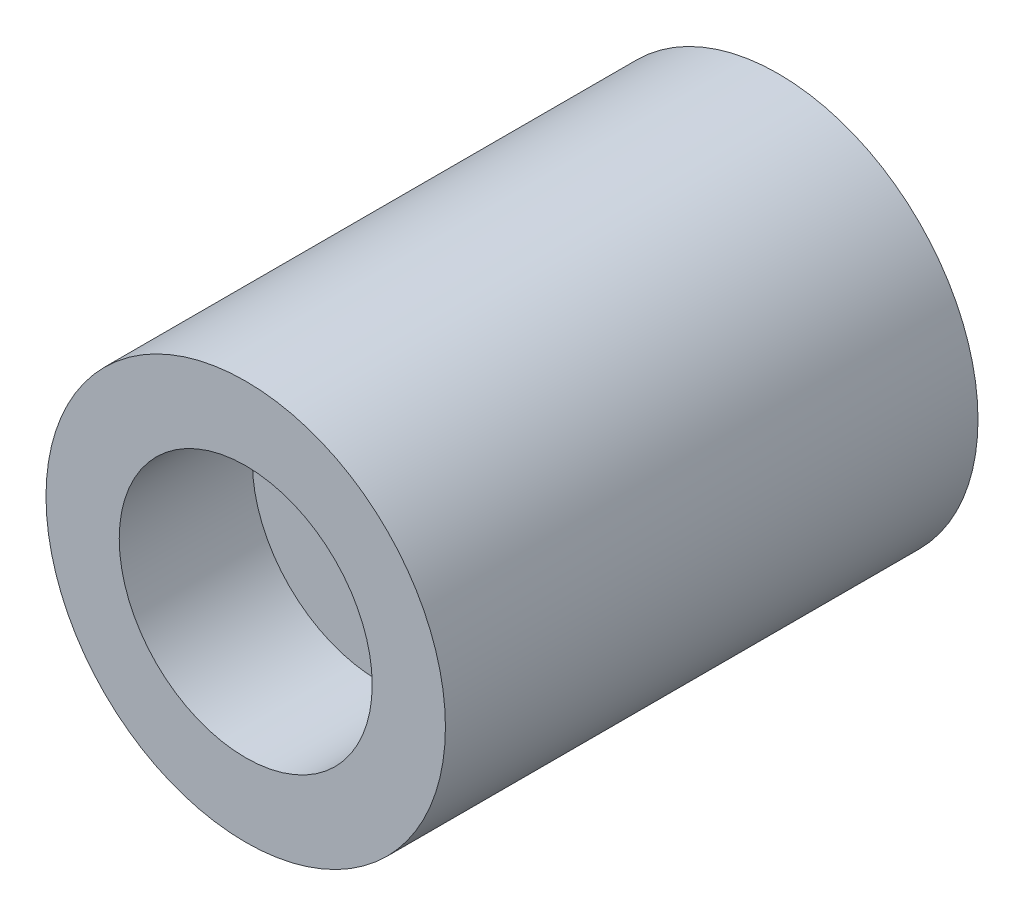
SolidWorks part; units mm, degrees
ref_plane "Front Plane" through (0, 0, 0) normal (1, 0, 0) x (0, 1, 0)
ref_plane "Top Plane" through (0, 0, 0) normal (0, 0, 1) x (0, 1, 0)
ref_plane "Right Plane" through (0, 0, 0) normal (0, 1, 0) x (-1, 0, 0)
sketch "Sketch1" plane through (0, 0, 0) normal (0, 0, 1) x (0, 1, 0)
  circle A0 centre (0, 0) radius 3
  circle A1 centre (0, 0) radius 1.1
  circle A2 centre (0, 0) radius 1.9
  dimension "D1" = 6
  dimension "ShaftDiameter" = 2.2
  dimension "D3" = 3.8
extrude "Boss-Extrude1" add sketch "Sketch1" along normal blind 8 contours A2 A1 | A0 A2 | A1 region at (0, -2.9151, 0) region at (0, 0, 0) region at (0, -1.8463, 0)
extrude "Cut-Extrude1" cut sketch "Sketch1<3>" against normal blind 2 from surface contours A2 A1 | A1 region at (0, 0, 0) region at (0, -1.8463, 0) starting at face at (3, 0, 8)
sketch "Sketch1<3>" plane through (0, 0, 0) normal (0, 0, 1) x (0, 1, 0) same geometry as "Sketch1"
extrude "Cut-Extrude2" cut sketch "Sketch1<4>" along normal blind 5 contours A1 region at (0, 0, 0)
sketch "Sketch1<4>" plane through (0, 0, 0) normal (0, 0, 1) x (0, 1, 0) same geometry as "Sketch1"
equation "\"MagnetDiameter\"= 3.8"
equation "\"BackShaftContainerDiameter\"=6"
equation "\"D3@Sketch1\"=\"MagnetDiameter\""
equation "\"D1@Sketch1\"=\"BackShaftContainerDiameter\""
equation "\"ShaftLength\"= 5"
equation "\"D1@Boss-Extrude1\"=\"ShaftLength\"+\"MagnetThickness\"+1"
equation "\"MagnetThickness\"=2"
equation "\"D1@Cut-Extrude1\"=\"MagnetThickness\""
equation "\"D1@Cut-Extrude2\"=\"ShaftLength\""
